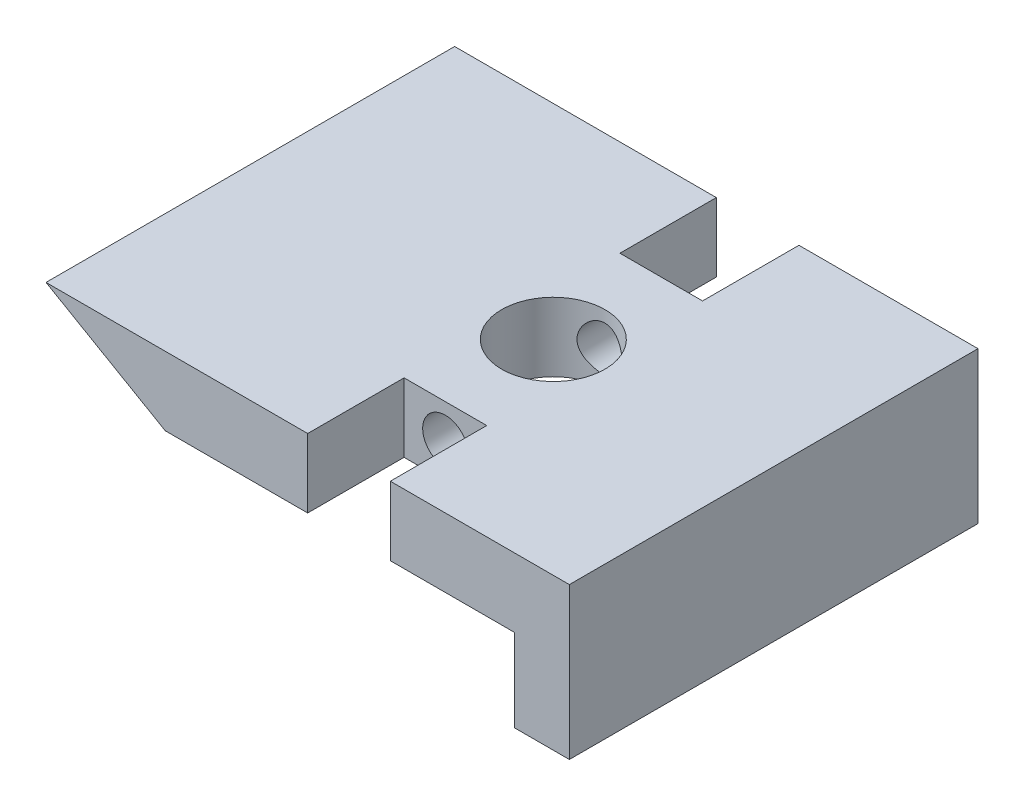
SolidWorks part; units mm, degrees
ref_plane "Front Plane" through (0, 0, 0) normal (0, 0, 1) x (1, 0, 0)
ref_plane "Top Plane" through (0, 0, 0) normal (0, 1, 0) x (1, 0, 0)
ref_plane "Right Plane" through (0, 0, 0) normal (1, 0, 0) x (0, 0, -1)
sketch "Sketch3" plane through (0, 0, 0) normal (0, 0, 1) x (1, 0, 0)
  line L0 (-19, 2.5) -> (-10.3397, -2.5)
  line L1 (-10.3397, -2.5) -> (19, -2.5)
  line L3 (-19, 2.5) -> (19, 2.5)
  line L4 (19, -2.5) -> (19, 2.5)
  line L5 (-11.9471, -1.572) -> (19, 2.5) construction
  line L6 (-19, 2.5) -> (19, -2.5) construction
  arc A0 (-19, 2.5) -> (-10.3397, -2.5) centre (-19, -7.5) cw construction
  point P0 (0, 0)
  point P6 (0, 2.5)
  dimension "D3" = 10
  dimension "D1" = 38
  dimension "D2" = 150
  dimension "D4" = 5
extrude "Boss-Extrude1" add sketch "Sketch3" along normal mid plane 29.67
sketch "Sketch4" plane through (0, 0, 14.835) normal (0, 0, 1) x (1, 0, 0)
  line L0 (19, -2.5) -> (19, 2.5) construction
  line L1 (19, 2.5) -> (-19, 2.5) construction
  line L2 (6, -2.5) -> (0, -2.5)
  line L3 (6, -2.5) -> (6, 2.5)
  line L4 (6, 2.5) -> (0, 2.5)
  line L5 (0, -2.5) -> (0, 2.5)
  line L6 (6, -2.5) -> (0, 2.5) construction
  line L7 (6, 2.5) -> (0, -2.5) construction
  circle A2 centre (3, 0) radius 1.65
  point P0 (19, 0)
  dimension "D1" = 3.3
  dimension "D5" = 16
extrude "Cut-Extrude1" cut sketch "Sketch4" against normal up to next contours A2 region at (3, 0, 14.835)
extrude "Cut-Extrude3" cut sketch "Sketch4<3>" against normal blind 7
sketch "Sketch4<3>" plane through (0, 0, 14.835) normal (0, 0, 1) x (1, 0, 0) same geometry as "Sketch4"
mirror "Mirror1" about plane through (0, 0, 0) normal (0, 0, 1) of "Cut-Extrude3"
sketch "Sketch5" plane through (0, 2.5, 0) normal (0, 1, 0) x (1, 0, 0)
  line L0 (19, -14.835) -> (19, 14.835) construction
  circle A0 centre (3, 0) radius 3.75
  point P7 (19, 0)
  dimension "D2" = 7.5
  dimension "D1" = 16
extrude "Cut-Extrude2" cut sketch "Sketch5" against normal up to next
sketch "Sketch6" plane through (0, 0, 14.835) normal (0, 0, 1) x (1, 0, 0)
  line L0 (19, -2.5) -> (19, -8.5)
  line L1 (19, -8.5) -> (15, -8.5)
  line L2 (15, -8.5) -> (15, -2.5)
  line L3 (-10.3397, -2.5) -> (0, -2.5) construction
  line L4 (15, -2.5) -> (19, -2.5)
  dimension "D1" = 6
  dimension "D2" = 4
extrude "Boss-Extrude2" add sketch "Sketch6" against normal up to surface (29.67 mm away) up to face at (-7.3349, 0, -14.835)
